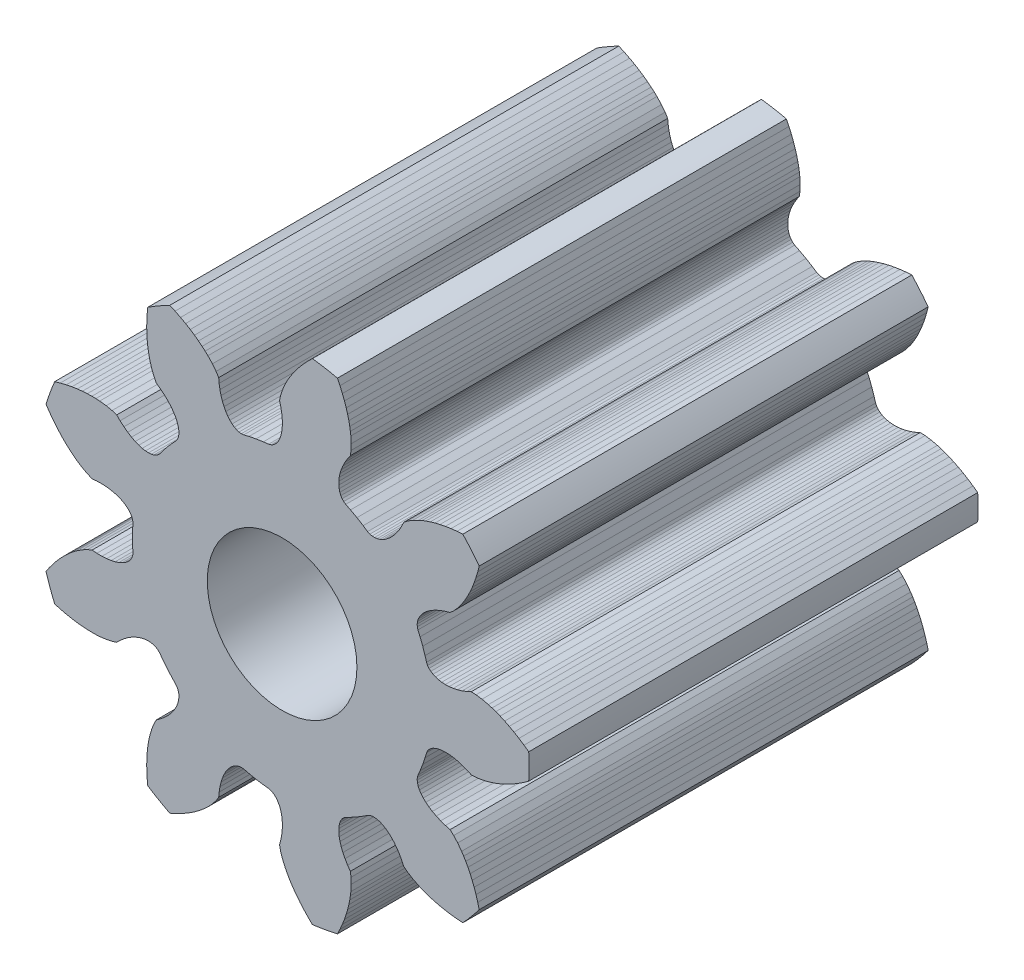
SolidWorks part; units mm, degrees
ref_plane "Plano frontal" through (0, 0, 0) normal (0, 0, 1) x (1, 0, 0)
ref_plane "Plano superior" through (0, 0, 0) normal (0, 1, 0) x (1, 0, 0)
ref_plane "Plano direito" through (0, 0, 0) normal (1, 0, 0) x (0, 0, -1)
sketch "Model" plane through (0, 0, 0) normal (0, 0, 1) x (1, 0, 0)
  line L0 (1.3073, 0.9564) -> (1.2957, 0.9175)
  line L1 (1.2957, 0.9175) -> (1.2833, 0.8811)
  line L2 (1.2833, 0.8811) -> (1.2701, 0.8472)
  line L3 (1.2701, 0.8472) -> (1.2565, 0.8161)
  line L4 (1.2565, 0.8161) -> (1.2419, 0.7863)
  line L5 (1.2419, 0.7863) -> (1.2271, 0.7591)
  line L6 (1.2271, 0.7591) -> (1.2133, 0.7361)
  line L7 (1.2133, 0.7361) -> (1.1993, 0.7148)
  line L8 (1.1993, 0.7148) -> (1.173, 0.6797)
  line L9 (1.173, 0.6797) -> (1.1464, 0.65)
  line L10 (1.1464, 0.65) -> (1.1223, 0.6281)
  line L11 (1.1223, 0.6281) -> (1.0915, 0.6196)
  line L12 (1.0915, 0.6196) -> (1.0595, 0.6085)
  line L13 (1.0595, 0.6085) -> (1.0303, 0.5958)
  line L14 (1.0303, 0.5958) -> (1.0041, 0.5819)
  line L15 (1.0041, 0.5819) -> (0.9808, 0.5669)
  line L16 (0.9808, 0.5669) -> (0.9605, 0.5511)
  line L17 (0.9605, 0.5511) -> (0.9433, 0.5347)
  line L18 (0.9433, 0.5347) -> (0.9291, 0.5179)
  line L19 (0.9291, 0.5179) -> (0.918, 0.501)
  line L20 (0.918, 0.501) -> (0.9099, 0.4841)
  line L21 (0.9099, 0.4841) -> (0.9048, 0.4675)
  line L22 (0.9048, 0.4675) -> (0.9027, 0.4515)
  line L23 (0.9027, 0.4515) -> (0.9034, 0.4362)
  line L24 (0.9034, 0.4362) -> (0.9076, 0.4201)
  line L25 (0.9076, 0.4201) -> (0.9219, 0.3875)
  line L26 (0.9219, 0.3875) -> (0.9397, 0.342)
  line L27 (0.9397, 0.342) -> (0.9553, 0.2957)
  line L28 (0.9553, 0.2957) -> (0.9653, 0.2616)
  line L29 (0.9653, 0.2616) -> (0.9724, 0.2466)
  line L30 (0.9724, 0.2466) -> (0.9817, 0.2344)
  line L31 (0.9817, 0.2344) -> (0.9937, 0.2234)
  line L32 (0.9937, 0.2234) -> (1.0082, 0.214)
  line L33 (1.0082, 0.214) -> (1.0253, 0.2063)
  line L34 (1.0253, 0.2063) -> (1.0447, 0.2005)
  line L35 (1.0447, 0.2005) -> (1.0663, 0.1968)
  line L36 (1.0663, 0.1968) -> (1.0901, 0.1953)
  line L37 (1.0901, 0.1953) -> (1.1158, 0.1962)
  line L38 (1.1158, 0.1962) -> (1.1432, 0.1997)
  line L39 (1.1432, 0.1997) -> (1.1723, 0.2059)
  line L40 (1.1723, 0.2059) -> (1.2027, 0.2149)
  line L41 (1.2027, 0.2149) -> (1.2344, 0.227)
  line L42 (1.2344, 0.227) -> (1.2635, 0.2403)
  line L43 (1.2635, 0.2403) -> (1.296, 0.239)
  line L44 (1.296, 0.239) -> (1.3355, 0.2333)
  line L45 (1.3355, 0.2333) -> (1.3782, 0.2233)
  line L46 (1.3782, 0.2233) -> (1.4026, 0.216)
  line L47 (1.4026, 0.216) -> (1.4279, 0.2073)
  line L48 (1.4279, 0.2073) -> (1.4567, 0.1959)
  line L49 (1.4567, 0.1959) -> (1.4871, 0.1825)
  line L50 (1.4871, 0.1825) -> (1.5175, 0.1674)
  line L51 (1.5175, 0.1674) -> (1.5494, 0.1499)
  line L52 (1.5494, 0.1499) -> (1.5823, 0.1301)
  line L53 (1.5823, 0.1301) -> (1.6162, 0.1077)
  line L54 (1.6162, 0.1077) -> (1.6478, 0.0849)
  line L55 (1.6478, -0.0849) -> (1.6162, -0.1077)
  line L56 (1.6162, -0.1077) -> (1.5823, -0.1301)
  line L57 (1.5823, -0.1301) -> (1.5494, -0.1499)
  line L58 (1.5494, -0.1499) -> (1.5175, -0.1674)
  line L59 (1.5175, -0.1674) -> (1.4871, -0.1825)
  line L60 (1.4871, -0.1825) -> (1.4567, -0.1959)
  line L61 (1.4567, -0.1959) -> (1.4279, -0.2073)
  line L62 (1.4279, -0.2073) -> (1.4026, -0.216)
  line L63 (1.4026, -0.216) -> (1.3782, -0.2233)
  line L64 (1.3782, -0.2233) -> (1.3355, -0.2333)
  line L65 (1.3355, -0.2333) -> (1.296, -0.239)
  line L66 (1.296, -0.239) -> (1.2635, -0.2403)
  line L67 (1.2635, -0.2403) -> (1.2344, -0.227)
  line L68 (1.2344, -0.227) -> (1.2027, -0.2149)
  line L69 (1.2027, -0.2149) -> (1.1723, -0.2059)
  line L70 (1.1723, -0.2059) -> (1.1432, -0.1997)
  line L71 (1.1432, -0.1997) -> (1.1158, -0.1962)
  line L72 (1.1158, -0.1962) -> (1.0901, -0.1953)
  line L73 (1.0901, -0.1953) -> (1.0663, -0.1968)
  line L74 (1.0663, -0.1968) -> (1.0447, -0.2005)
  line L75 (1.0447, -0.2005) -> (1.0253, -0.2063)
  line L76 (1.0253, -0.2063) -> (1.0082, -0.214)
  line L77 (1.0082, -0.214) -> (0.9937, -0.2234)
  line L78 (0.9937, -0.2234) -> (0.9817, -0.2344)
  line L79 (0.9817, -0.2344) -> (0.9724, -0.2466)
  line L80 (0.9724, -0.2466) -> (0.9653, -0.2616)
  line L81 (0.9653, -0.2616) -> (0.9553, -0.2957)
  line L82 (0.9553, -0.2957) -> (0.9397, -0.342)
  line L83 (0.9397, -0.342) -> (0.9219, -0.3875)
  line L84 (0.9219, -0.3875) -> (0.9076, -0.4201)
  line L85 (0.9076, -0.4201) -> (0.9034, -0.4362)
  line L86 (0.9034, -0.4362) -> (0.9027, -0.4515)
  line L87 (0.9027, -0.4515) -> (0.9048, -0.4675)
  line L88 (0.9048, -0.4675) -> (0.9099, -0.4841)
  line L89 (0.9099, -0.4841) -> (0.918, -0.501)
  line L90 (0.918, -0.501) -> (0.9291, -0.5179)
  line L91 (0.9291, -0.5179) -> (0.9433, -0.5347)
  line L92 (0.9433, -0.5347) -> (0.9605, -0.5511)
  line L93 (0.9605, -0.5511) -> (0.9808, -0.5669)
  line L94 (0.9808, -0.5669) -> (1.0041, -0.5819)
  line L95 (1.0041, -0.5819) -> (1.0303, -0.5958)
  line L96 (1.0303, -0.5958) -> (1.0595, -0.6085)
  line L97 (1.0595, -0.6085) -> (1.0915, -0.6196)
  line L98 (1.0915, -0.6196) -> (1.1223, -0.6281)
  line L99 (1.1223, -0.6281) -> (1.1464, -0.65)
  line L100 (1.1464, -0.65) -> (1.173, -0.6797)
  line L101 (1.173, -0.6797) -> (1.1993, -0.7148)
  line L102 (1.1993, -0.7148) -> (1.2133, -0.7361)
  line L103 (1.2133, -0.7361) -> (1.2271, -0.7591)
  line L104 (1.2271, -0.7591) -> (1.2419, -0.7863)
  line L105 (1.2419, -0.7863) -> (1.2565, -0.8161)
  line L106 (1.2565, -0.8161) -> (1.2701, -0.8472)
  line L107 (1.2701, -0.8472) -> (1.2833, -0.8811)
  line L108 (1.2833, -0.8811) -> (1.2957, -0.9175)
  line L109 (1.2957, -0.9175) -> (1.3073, -0.9564)
  line L110 (1.3073, -0.9564) -> (1.3169, -0.9941)
  line L111 (1.2077, -1.1242) -> (1.1689, -1.1214)
  line L112 (1.1689, -1.1214) -> (1.1285, -1.1167)
  line L113 (1.1285, -1.1167) -> (1.0905, -1.1108)
  line L114 (1.0905, -1.1108) -> (1.0549, -1.1037)
  line L115 (1.0549, -1.1037) -> (1.0218, -1.0957)
  line L116 (1.0218, -1.0957) -> (0.99, -1.0865)
  line L117 (0.99, -1.0865) -> (0.9606, -1.0766)
  line L118 (0.9606, -1.0766) -> (0.9356, -1.067)
  line L119 (0.9356, -1.067) -> (0.9122, -1.057)
  line L120 (0.9122, -1.057) -> (0.8731, -1.0372)
  line L121 (0.8731, -1.0372) -> (0.8392, -1.0161)
  line L122 (0.8392, -1.0161) -> (0.8134, -0.9962)
  line L123 (0.8134, -0.9962) -> (0.7997, -0.9674)
  line L124 (0.7997, -0.9674) -> (0.7832, -0.9378)
  line L125 (0.7832, -0.9378) -> (0.7657, -0.9112)
  line L126 (0.7657, -0.9112) -> (0.7474, -0.8878)
  line L127 (0.7474, -0.8878) -> (0.7286, -0.8675)
  line L128 (0.7286, -0.8675) -> (0.7095, -0.8503)
  line L129 (0.7095, -0.8503) -> (0.6904, -0.8361)
  line L130 (0.6904, -0.8361) -> (0.6714, -0.8251)
  line L131 (0.6714, -0.8251) -> (0.6528, -0.8171)
  line L132 (0.6528, -0.8171) -> (0.6348, -0.812)
  line L133 (0.6348, -0.812) -> (0.6176, -0.8099)
  line L134 (0.6176, -0.8099) -> (0.6014, -0.8105)
  line L135 (0.6014, -0.8105) -> (0.5864, -0.8139)
  line L136 (0.5864, -0.8139) -> (0.5713, -0.8209)
  line L137 (0.5713, -0.8209) -> (0.5417, -0.8406)
  line L138 (0.5417, -0.8406) -> (0.5, -0.866)
  line L139 (0.5, -0.866) -> (0.4571, -0.8894)
  line L140 (0.4571, -0.8894) -> (0.4253, -0.9052)
  line L141 (0.4253, -0.9052) -> (0.4117, -0.9148)
  line L142 (0.4117, -0.9148) -> (0.4013, -0.9261)
  line L143 (0.4013, -0.9261) -> (0.3926, -0.9398)
  line L144 (0.3926, -0.9398) -> (0.3858, -0.9557)
  line L145 (0.3858, -0.9557) -> (0.3812, -0.9739)
  line L146 (0.3812, -0.9739) -> (0.3789, -0.994)
  line L147 (0.3789, -0.994) -> (0.3789, -1.016)
  line L148 (0.3789, -1.016) -> (0.3816, -1.0396)
  line L149 (0.3816, -1.0396) -> (0.3869, -1.0647)
  line L150 (0.3869, -1.0647) -> (0.3951, -1.0912)
  line L151 (0.3951, -1.0912) -> (0.4063, -1.1187)
  line L152 (0.4063, -1.1187) -> (0.4205, -1.1472)
  line L153 (0.4205, -1.1472) -> (0.4379, -1.1763)
  line L154 (0.4379, -1.1763) -> (0.456, -1.2025)
  line L155 (0.456, -1.2025) -> (0.4604, -1.2348)
  line L156 (0.4604, -1.2348) -> (0.4617, -1.2747)
  line L157 (0.4617, -1.2747) -> (0.4592, -1.3185)
  line L158 (0.4592, -1.3185) -> (0.4563, -1.3438)
  line L159 (0.4563, -1.3438) -> (0.4521, -1.3702)
  line L160 (0.4521, -1.3702) -> (0.4459, -1.4006)
  line L161 (0.4459, -1.4006) -> (0.4379, -1.4328)
  line L162 (0.4379, -1.4328) -> (0.4284, -1.4654)
  line L163 (0.4284, -1.4654) -> (0.4167, -1.4998)
  line L164 (0.4167, -1.4998) -> (0.4029, -1.5357)
  line L165 (0.4029, -1.5357) -> (0.3867, -1.573)
  line L166 (0.3867, -1.573) -> (0.3698, -1.608)
  line L167 (0.2025, -1.6375) -> (0.1746, -1.6104)
  line L168 (0.1746, -1.6104) -> (0.1467, -1.5809)
  line L169 (0.1467, -1.5809) -> (0.1214, -1.5519)
  line L170 (0.1214, -1.5519) -> (0.0986, -1.5235)
  line L171 (0.0986, -1.5235) -> (0.0785, -1.4962)
  line L172 (0.0785, -1.4962) -> (0.06, -1.4686)
  line L173 (0.06, -1.4686) -> (0.0438, -1.4422)
  line L174 (0.0438, -1.4422) -> (0.0308, -1.4188)
  line L175 (0.0308, -1.4188) -> (0.0194, -1.3961)
  line L176 (0.0194, -1.3961) -> (0.0021, -1.3557)
  line L177 (0.0021, -1.3557) -> (-0.0103, -1.3178)
  line L178 (-0.0103, -1.3178) -> (-0.0172, -1.286)
  line L179 (-0.0172, -1.286) -> (-0.0092, -1.2551)
  line L180 (-0.0092, -1.2551) -> (-0.0028, -1.2218)
  line L181 (-0.0028, -1.2218) -> (0.0008, -1.1902)
  line L182 (0.0008, -1.1902) -> (0.0019, -1.1605)
  line L183 (0.0019, -1.1605) -> (0.0006, -1.1329)
  line L184 (0.0006, -1.1329) -> (-0.003, -1.1074)
  line L185 (-0.003, -1.1074) -> (-0.0086, -1.0843)
  line L186 (-0.0086, -1.0843) -> (-0.016, -1.0636)
  line L187 (-0.016, -1.0636) -> (-0.0252, -1.0455)
  line L188 (-0.0252, -1.0455) -> (-0.0357, -1.0301)
  line L189 (-0.0357, -1.0301) -> (-0.0475, -1.0174)
  line L190 (-0.0475, -1.0174) -> (-0.0603, -1.0075)
  line L191 (-0.0603, -1.0075) -> (-0.074, -1.0005)
  line L192 (-0.074, -1.0005) -> (-0.09, -0.9961)
  line L193 (-0.09, -0.9961) -> (-0.1253, -0.9921)
  line L194 (-0.1253, -0.9921) -> (-0.1736, -0.9848)
  line L195 (-0.1736, -0.9848) -> (-0.2215, -0.9752)
  line L196 (-0.2215, -0.9752) -> (-0.2561, -0.9668)
  line L197 (-0.2561, -0.9668) -> (-0.2727, -0.9654)
  line L198 (-0.2727, -0.9654) -> (-0.2879, -0.9673)
  line L199 (-0.2879, -0.9673) -> (-0.3033, -0.9723)
  line L200 (-0.3033, -0.9723) -> (-0.3188, -0.9801)
  line L201 (-0.3188, -0.9801) -> (-0.334, -0.9911)
  line L202 (-0.334, -0.9911) -> (-0.3487, -1.005)
  line L203 (-0.3487, -1.005) -> (-0.3628, -1.0218)
  line L204 (-0.3628, -1.0218) -> (-0.3759, -1.0417)
  line L205 (-0.3759, -1.0417) -> (-0.388, -1.0644)
  line L206 (-0.388, -1.0644) -> (-0.3987, -1.0899)
  line L207 (-0.3987, -1.0899) -> (-0.4079, -1.1181)
  line L208 (-0.4079, -1.1181) -> (-0.4152, -1.1491)
  line L209 (-0.4152, -1.1491) -> (-0.4207, -1.1825)
  line L210 (-0.4207, -1.1825) -> (-0.4237, -1.2143)
  line L211 (-0.4237, -1.2143) -> (-0.4411, -1.2419)
  line L212 (-0.4411, -1.2419) -> (-0.4657, -1.2732)
  line L213 (-0.4657, -1.2732) -> (-0.4957, -1.3052)
  line L214 (-0.4957, -1.3052) -> (-0.5142, -1.3227)
  line L215 (-0.5142, -1.3227) -> (-0.5345, -1.3402)
  line L216 (-0.5345, -1.3402) -> (-0.5587, -1.3595)
  line L217 (-0.5587, -1.3595) -> (-0.5855, -1.3791)
  line L218 (-0.5855, -1.3791) -> (-0.6138, -1.3979)
  line L219 (-0.6138, -1.3979) -> (-0.6449, -1.4168)
  line L220 (-0.6449, -1.4168) -> (-0.6785, -1.4354)
  line L221 (-0.6785, -1.4354) -> (-0.7149, -1.4535)
  line L222 (-0.7149, -1.4535) -> (-0.7504, -1.4695)
  line L223 (-0.8974, -1.3846) -> (-0.9014, -1.3458)
  line L224 (-0.9014, -1.3458) -> (-0.9038, -1.3053)
  line L225 (-0.9038, -1.3053) -> (-0.9046, -1.2669)
  line L226 (-0.9046, -1.2669) -> (-0.9037, -1.2305)
  line L227 (-0.9037, -1.2305) -> (-0.9016, -1.1966)
  line L228 (-0.9016, -1.1966) -> (-0.898, -1.1636)
  line L229 (-0.898, -1.1636) -> (-0.8934, -1.133)
  line L230 (-0.8934, -1.133) -> (-0.8884, -1.1067)
  line L231 (-0.8884, -1.1067) -> (-0.8825, -1.0819)
  line L232 (-0.8825, -1.0819) -> (-0.8698, -1.0399)
  line L233 (-0.8698, -1.0399) -> (-0.855, -1.0029)
  line L234 (-0.855, -1.0029) -> (-0.8398, -0.9741)
  line L235 (-0.8398, -0.9741) -> (-0.8138, -0.9556)
  line L236 (-0.8138, -0.9556) -> (-0.7875, -0.9341)
  line L237 (-0.7875, -0.9341) -> (-0.7644, -0.9123)
  line L238 (-0.7644, -0.9123) -> (-0.7445, -0.8902)
  line L239 (-0.7445, -0.8902) -> (-0.7278, -0.8682)
  line L240 (-0.7278, -0.8682) -> (-0.7141, -0.8464)
  line L241 (-0.7141, -0.8464) -> (-0.7036, -0.8251)
  line L242 (-0.7036, -0.8251) -> (-0.696, -0.8045)
  line L243 (-0.696, -0.8045) -> (-0.6913, -0.7847)
  line L244 (-0.6913, -0.7847) -> (-0.6895, -0.7661)
  line L245 (-0.6895, -0.7661) -> (-0.6903, -0.7488)
  line L246 (-0.6903, -0.7488) -> (-0.6938, -0.733)
  line L247 (-0.6938, -0.733) -> (-0.6998, -0.7189)
  line L248 (-0.6998, -0.7189) -> (-0.7092, -0.7052)
  line L249 (-0.7092, -0.7052) -> (-0.7337, -0.6794)
  line L250 (-0.7337, -0.6794) -> (-0.766, -0.6428)
  line L251 (-0.766, -0.6428) -> (-0.7965, -0.6046)
  line L252 (-0.7965, -0.6046) -> (-0.8176, -0.576)
  line L253 (-0.8176, -0.576) -> (-0.8294, -0.5643)
  line L254 (-0.8294, -0.5643) -> (-0.8423, -0.556)
  line L255 (-0.8423, -0.556) -> (-0.8573, -0.5498)
  line L256 (-0.8573, -0.5498) -> (-0.8742, -0.5459)
  line L257 (-0.8742, -0.5459) -> (-0.8929, -0.5445)
  line L258 (-0.8929, -0.5445) -> (-0.9131, -0.5457)
  line L259 (-0.9131, -0.5457) -> (-0.9347, -0.5496)
  line L260 (-0.9347, -0.5496) -> (-0.9576, -0.5563)
  line L261 (-0.9576, -0.5563) -> (-0.9814, -0.566)
  line L262 (-0.9814, -0.566) -> (-1.006, -0.5786)
  line L263 (-1.006, -0.5786) -> (-1.0312, -0.5944)
  line L264 (-1.0312, -0.5944) -> (-1.0567, -0.6133)
  line L265 (-1.0567, -0.6133) -> (-1.0824, -0.6355)
  line L266 (-1.0824, -0.6355) -> (-1.1051, -0.6579)
  line L267 (-1.1051, -0.6579) -> (-1.1361, -0.6678)
  line L268 (-1.1361, -0.6678) -> (-1.1752, -0.676)
  line L269 (-1.1752, -0.676) -> (-1.2187, -0.6812)
  line L270 (-1.2187, -0.6812) -> (-1.2441, -0.6827)
  line L271 (-1.2441, -0.6827) -> (-1.2709, -0.6831)
  line L272 (-1.2709, -0.6831) -> (-1.3018, -0.6824)
  line L273 (-1.3018, -0.6824) -> (-1.335, -0.6801)
  line L274 (-1.335, -0.6801) -> (-1.3687, -0.6763)
  line L275 (-1.3687, -0.6763) -> (-1.4047, -0.6708)
  line L276 (-1.4047, -0.6708) -> (-1.4424, -0.6634)
  line L277 (-1.4424, -0.6634) -> (-1.4819, -0.654)
  line L278 (-1.4819, -0.654) -> (-1.5194, -0.6434)
  line L279 (-1.5775, -0.4838) -> (-1.5556, -0.4516)
  line L280 (-1.5556, -0.4516) -> (-1.5314, -0.419)
  line L281 (-1.5314, -0.419) -> (-1.5072, -0.389)
  line L282 (-1.5072, -0.389) -> (-1.4832, -0.3617)
  line L283 (-1.4832, -0.3617) -> (-1.4598, -0.3371)
  line L284 (-1.4598, -0.3371) -> (-1.4359, -0.3141)
  line L285 (-1.4359, -0.3141) -> (-1.4127, -0.2936)
  line L286 (-1.4127, -0.2936) -> (-1.3919, -0.2767)
  line L287 (-1.3919, -0.2767) -> (-1.3715, -0.2615)
  line L288 (-1.3715, -0.2615) -> (-1.3348, -0.2375)
  line L289 (-1.3348, -0.2375) -> (-1.2996, -0.2187)
  line L290 (-1.2996, -0.2187) -> (-1.2694, -0.2064)
  line L291 (-1.2694, -0.2064) -> (-1.2376, -0.2089)
  line L292 (-1.2376, -0.2089) -> (-1.2037, -0.2094)
  line L293 (-1.2037, -0.2094) -> (-1.172, -0.2075)
  line L294 (-1.172, -0.2075) -> (-1.1425, -0.2034)
  line L295 (-1.1425, -0.2034) -> (-1.1156, -0.1973)
  line L296 (-1.1156, -0.1973) -> (-1.0911, -0.1893)
  line L297 (-1.0911, -0.1893) -> (-1.0693, -0.1798)
  line L298 (-1.0693, -0.1798) -> (-1.0502, -0.1689)
  line L299 (-1.0502, -0.1689) -> (-1.034, -0.1568)
  line L300 (-1.034, -0.1568) -> (-1.0206, -0.1437)
  line L301 (-1.0206, -0.1437) -> (-1.0102, -0.1299)
  line L302 (-1.0102, -0.1299) -> (-1.0026, -0.1155)
  line L303 (-1.0026, -0.1155) -> (-0.9981, -0.1009)
  line L304 (-0.9981, -0.1009) -> (-0.9966, -0.0843)
  line L305 (-0.9966, -0.0843) -> (-0.9988, -0.0488)
  line L306 (-0.9988, -0.0488) -> (-1, 0)
  line L307 (-1, 0) -> (-0.9988, 0.0488)
  line L308 (-0.9988, 0.0488) -> (-0.9966, 0.0843)
  line L309 (-0.9966, 0.0843) -> (-0.9981, 0.1009)
  line L310 (-0.9981, 0.1009) -> (-1.0026, 0.1155)
  line L311 (-1.0026, 0.1155) -> (-1.0102, 0.1299)
  line L312 (-1.0102, 0.1299) -> (-1.0206, 0.1437)
  line L313 (-1.0206, 0.1437) -> (-1.034, 0.1568)
  line L314 (-1.034, 0.1568) -> (-1.0502, 0.1689)
  line L315 (-1.0502, 0.1689) -> (-1.0693, 0.1798)
  line L316 (-1.0693, 0.1798) -> (-1.0911, 0.1893)
  line L317 (-1.0911, 0.1893) -> (-1.1156, 0.1973)
  line L318 (-1.1156, 0.1973) -> (-1.1425, 0.2034)
  line L319 (-1.1425, 0.2034) -> (-1.172, 0.2075)
  line L320 (-1.172, 0.2075) -> (-1.2037, 0.2094)
  line L321 (-1.2037, 0.2094) -> (-1.2376, 0.2089)
  line L322 (-1.2376, 0.2089) -> (-1.2694, 0.2064)
  line L323 (-1.2694, 0.2064) -> (-1.2996, 0.2187)
  line L324 (-1.2996, 0.2187) -> (-1.3348, 0.2375)
  line L325 (-1.3348, 0.2375) -> (-1.3715, 0.2615)
  line L326 (-1.3715, 0.2615) -> (-1.3919, 0.2767)
  line L327 (-1.3919, 0.2767) -> (-1.4127, 0.2936)
  line L328 (-1.4127, 0.2936) -> (-1.4359, 0.3141)
  line L329 (-1.4359, 0.3141) -> (-1.4598, 0.3371)
  line L330 (-1.4598, 0.3371) -> (-1.4832, 0.3617)
  line L331 (-1.4832, 0.3617) -> (-1.5072, 0.389)
  line L332 (-1.5072, 0.389) -> (-1.5314, 0.419)
  line L333 (-1.5314, 0.419) -> (-1.5556, 0.4516)
  line L334 (-1.5556, 0.4516) -> (-1.5775, 0.4838)
  line L335 (-1.5194, 0.6434) -> (-1.4819, 0.654)
  line L336 (-1.4819, 0.654) -> (-1.4424, 0.6634)
  line L337 (-1.4424, 0.6634) -> (-1.4047, 0.6708)
  line L338 (-1.4047, 0.6708) -> (-1.3687, 0.6763)
  line L339 (-1.3687, 0.6763) -> (-1.335, 0.6801)
  line L340 (-1.335, 0.6801) -> (-1.3018, 0.6824)
  line L341 (-1.3018, 0.6824) -> (-1.2709, 0.6831)
  line L342 (-1.2709, 0.6831) -> (-1.2441, 0.6827)
  line L343 (-1.2441, 0.6827) -> (-1.2187, 0.6812)
  line L344 (-1.2187, 0.6812) -> (-1.1752, 0.676)
  line L345 (-1.1752, 0.676) -> (-1.1361, 0.6678)
  line L346 (-1.1361, 0.6678) -> (-1.1051, 0.6579)
  line L347 (-1.1051, 0.6579) -> (-1.0824, 0.6355)
  line L348 (-1.0824, 0.6355) -> (-1.0567, 0.6133)
  line L349 (-1.0567, 0.6133) -> (-1.0312, 0.5944)
  line L350 (-1.0312, 0.5944) -> (-1.006, 0.5786)
  line L351 (-1.006, 0.5786) -> (-0.9814, 0.566)
  line L352 (-0.9814, 0.566) -> (-0.9576, 0.5563)
  line L353 (-0.9576, 0.5563) -> (-0.9347, 0.5496)
  line L354 (-0.9347, 0.5496) -> (-0.9131, 0.5457)
  line L355 (-0.9131, 0.5457) -> (-0.8929, 0.5445)
  line L356 (-0.8929, 0.5445) -> (-0.8742, 0.5459)
  line L357 (-0.8742, 0.5459) -> (-0.8573, 0.5498)
  line L358 (-0.8573, 0.5498) -> (-0.8423, 0.556)
  line L359 (-0.8423, 0.556) -> (-0.8294, 0.5643)
  line L360 (-0.8294, 0.5643) -> (-0.8176, 0.576)
  line L361 (-0.8176, 0.576) -> (-0.7965, 0.6046)
  line L362 (-0.7965, 0.6046) -> (-0.766, 0.6428)
  line L363 (-0.766, 0.6428) -> (-0.7337, 0.6794)
  line L364 (-0.7337, 0.6794) -> (-0.7092, 0.7052)
  line L365 (-0.7092, 0.7052) -> (-0.6998, 0.7189)
  line L366 (-0.6998, 0.7189) -> (-0.6938, 0.733)
  line L367 (-0.6938, 0.733) -> (-0.6903, 0.7488)
  line L368 (-0.6903, 0.7488) -> (-0.6895, 0.7661)
  line L369 (-0.6895, 0.7661) -> (-0.6913, 0.7847)
  line L370 (-0.6913, 0.7847) -> (-0.696, 0.8045)
  line L371 (-0.696, 0.8045) -> (-0.7036, 0.8251)
  line L372 (-0.7036, 0.8251) -> (-0.7141, 0.8464)
  line L373 (-0.7141, 0.8464) -> (-0.7278, 0.8682)
  line L374 (-0.7278, 0.8682) -> (-0.7445, 0.8902)
  line L375 (-0.7445, 0.8902) -> (-0.7644, 0.9123)
  line L376 (-0.7644, 0.9123) -> (-0.7875, 0.9341)
  line L377 (-0.7875, 0.9341) -> (-0.8138, 0.9556)
  line L378 (-0.8138, 0.9556) -> (-0.8398, 0.9741)
  line L379 (-0.8398, 0.9741) -> (-0.855, 1.0029)
  line L380 (-0.855, 1.0029) -> (-0.8698, 1.0399)
  line L381 (-0.8698, 1.0399) -> (-0.8825, 1.0819)
  line L382 (-0.8825, 1.0819) -> (-0.8884, 1.1067)
  line L383 (-0.8884, 1.1067) -> (-0.8934, 1.133)
  line L384 (-0.8934, 1.133) -> (-0.898, 1.1636)
  line L385 (-0.898, 1.1636) -> (-0.9016, 1.1966)
  line L386 (-0.9016, 1.1966) -> (-0.9037, 1.2305)
  line L387 (-0.9037, 1.2305) -> (-0.9046, 1.2669)
  line L388 (-0.9046, 1.2669) -> (-0.9038, 1.3053)
  line L389 (-0.9038, 1.3053) -> (-0.9014, 1.3458)
  line L390 (-0.9014, 1.3458) -> (-0.8974, 1.3846)
  line L391 (-0.7504, 1.4695) -> (-0.7149, 1.4535)
  line L392 (-0.7149, 1.4535) -> (-0.6785, 1.4354)
  line L393 (-0.6785, 1.4354) -> (-0.6449, 1.4168)
  line L394 (-0.6449, 1.4168) -> (-0.6138, 1.3979)
  line L395 (-0.6138, 1.3979) -> (-0.5855, 1.3791)
  line L396 (-0.5855, 1.3791) -> (-0.5587, 1.3595)
  line L397 (-0.5587, 1.3595) -> (-0.5345, 1.3402)
  line L398 (-0.5345, 1.3402) -> (-0.5142, 1.3227)
  line L399 (-0.5142, 1.3227) -> (-0.4957, 1.3052)
  line L400 (-0.4957, 1.3052) -> (-0.4657, 1.2732)
  line L401 (-0.4657, 1.2732) -> (-0.4411, 1.2419)
  line L402 (-0.4411, 1.2419) -> (-0.4237, 1.2143)
  line L403 (-0.4237, 1.2143) -> (-0.4207, 1.1825)
  line L404 (-0.4207, 1.1825) -> (-0.4152, 1.1491)
  line L405 (-0.4152, 1.1491) -> (-0.4079, 1.1181)
  line L406 (-0.4079, 1.1181) -> (-0.3987, 1.0899)
  line L407 (-0.3987, 1.0899) -> (-0.388, 1.0644)
  line L408 (-0.388, 1.0644) -> (-0.3759, 1.0417)
  line L409 (-0.3759, 1.0417) -> (-0.3628, 1.0218)
  line L410 (-0.3628, 1.0218) -> (-0.3487, 1.005)
  line L411 (-0.3487, 1.005) -> (-0.334, 0.9911)
  line L412 (-0.334, 0.9911) -> (-0.3188, 0.9801)
  line L413 (-0.3188, 0.9801) -> (-0.3033, 0.9723)
  line L414 (-0.3033, 0.9723) -> (-0.2879, 0.9673)
  line L415 (-0.2879, 0.9673) -> (-0.2727, 0.9654)
  line L416 (-0.2727, 0.9654) -> (-0.2561, 0.9668)
  line L417 (-0.2561, 0.9668) -> (-0.2215, 0.9752)
  line L418 (-0.2215, 0.9752) -> (-0.1736, 0.9848)
  line L419 (-0.1736, 0.9848) -> (-0.1253, 0.9921)
  line L420 (-0.1253, 0.9921) -> (-0.09, 0.9961)
  line L421 (-0.09, 0.9961) -> (-0.074, 1.0005)
  line L422 (-0.074, 1.0005) -> (-0.0603, 1.0075)
  line L423 (-0.0603, 1.0075) -> (-0.0475, 1.0174)
  line L424 (-0.0475, 1.0174) -> (-0.0357, 1.0301)
  line L425 (-0.0357, 1.0301) -> (-0.0252, 1.0455)
  line L426 (-0.0252, 1.0455) -> (-0.016, 1.0636)
  line L427 (-0.016, 1.0636) -> (-0.0086, 1.0843)
  line L428 (-0.0086, 1.0843) -> (-0.003, 1.1074)
  line L429 (-0.003, 1.1074) -> (0.0006, 1.1329)
  line L430 (0.0006, 1.1329) -> (0.0019, 1.1605)
  line L431 (0.0019, 1.1605) -> (0.0008, 1.1902)
  line L432 (0.0008, 1.1902) -> (-0.0028, 1.2218)
  line L433 (-0.0028, 1.2218) -> (-0.0092, 1.2551)
  line L434 (-0.0092, 1.2551) -> (-0.0172, 1.286)
  line L435 (-0.0172, 1.286) -> (-0.0103, 1.3178)
  line L436 (-0.0103, 1.3178) -> (0.0021, 1.3557)
  line L437 (0.0021, 1.3557) -> (0.0194, 1.3961)
  line L438 (0.0194, 1.3961) -> (0.0308, 1.4188)
  line L439 (0.0308, 1.4188) -> (0.0438, 1.4422)
  line L440 (0.0438, 1.4422) -> (0.06, 1.4686)
  line L441 (0.06, 1.4686) -> (0.0785, 1.4962)
  line L442 (0.0785, 1.4962) -> (0.0986, 1.5235)
  line L443 (0.0986, 1.5235) -> (0.1214, 1.5519)
  line L444 (0.1214, 1.5519) -> (0.1467, 1.5809)
  line L445 (0.1467, 1.5809) -> (0.1746, 1.6104)
  line L446 (0.1746, 1.6104) -> (0.2025, 1.6375)
  line L447 (0.3698, 1.608) -> (0.3867, 1.573)
  line L448 (0.3867, 1.573) -> (0.4029, 1.5357)
  line L449 (0.4029, 1.5357) -> (0.4167, 1.4998)
  line L450 (0.4167, 1.4998) -> (0.4284, 1.4654)
  line L451 (0.4284, 1.4654) -> (0.4379, 1.4328)
  line L452 (0.4379, 1.4328) -> (0.4459, 1.4006)
  line L453 (0.4459, 1.4006) -> (0.4521, 1.3702)
  line L454 (0.4521, 1.3702) -> (0.4563, 1.3438)
  line L455 (0.4563, 1.3438) -> (0.4592, 1.3185)
  line L456 (0.4592, 1.3185) -> (0.4617, 1.2747)
  line L457 (0.4617, 1.2747) -> (0.4604, 1.2348)
  line L458 (0.4604, 1.2348) -> (0.456, 1.2025)
  line L459 (0.456, 1.2025) -> (0.4379, 1.1763)
  line L460 (0.4379, 1.1763) -> (0.4205, 1.1472)
  line L461 (0.4205, 1.1472) -> (0.4063, 1.1187)
  line L462 (0.4063, 1.1187) -> (0.3951, 1.0912)
  line L463 (0.3951, 1.0912) -> (0.3869, 1.0647)
  line L464 (0.3869, 1.0647) -> (0.3816, 1.0396)
  line L465 (0.3816, 1.0396) -> (0.3789, 1.016)
  line L466 (0.3789, 1.016) -> (0.3789, 0.994)
  line L467 (0.3789, 0.994) -> (0.3812, 0.9739)
  line L468 (0.3812, 0.9739) -> (0.3858, 0.9557)
  line L469 (0.3858, 0.9557) -> (0.3926, 0.9398)
  line L470 (0.3926, 0.9398) -> (0.4013, 0.9261)
  line L471 (0.4013, 0.9261) -> (0.4117, 0.9148)
  line L472 (0.4117, 0.9148) -> (0.4253, 0.9052)
  line L473 (0.4253, 0.9052) -> (0.4571, 0.8894)
  line L474 (0.4571, 0.8894) -> (0.5, 0.866)
  line L475 (0.5, 0.866) -> (0.5417, 0.8406)
  line L476 (0.5417, 0.8406) -> (0.5713, 0.8209)
  line L477 (0.5713, 0.8209) -> (0.5864, 0.8139)
  line L478 (0.5864, 0.8139) -> (0.6014, 0.8105)
  line L479 (0.6014, 0.8105) -> (0.6176, 0.8099)
  line L480 (0.6176, 0.8099) -> (0.6348, 0.812)
  line L481 (0.6348, 0.812) -> (0.6528, 0.8171)
  line L482 (0.6528, 0.8171) -> (0.6714, 0.8251)
  line L483 (0.6714, 0.8251) -> (0.6904, 0.8361)
  line L484 (0.6904, 0.8361) -> (0.7095, 0.8503)
  line L485 (0.7095, 0.8503) -> (0.7286, 0.8675)
  line L486 (0.7286, 0.8675) -> (0.7474, 0.8878)
  line L487 (0.7474, 0.8878) -> (0.7657, 0.9112)
  line L488 (0.7657, 0.9112) -> (0.7832, 0.9378)
  line L489 (0.7832, 0.9378) -> (0.7997, 0.9674)
  line L490 (0.7997, 0.9674) -> (0.8134, 0.9962)
  line L491 (0.8134, 0.9962) -> (0.8392, 1.0161)
  line L492 (0.8392, 1.0161) -> (0.8731, 1.0372)
  line L493 (0.8731, 1.0372) -> (0.9122, 1.057)
  line L494 (0.9122, 1.057) -> (0.9356, 1.067)
  line L495 (0.9356, 1.067) -> (0.9606, 1.0766)
  line L496 (0.9606, 1.0766) -> (0.99, 1.0865)
  line L497 (0.99, 1.0865) -> (1.0218, 1.0957)
  line L498 (1.0218, 1.0957) -> (1.0549, 1.1037)
  line L499 (1.0549, 1.1037) -> (1.0905, 1.1108)
  line L500 (1.0905, 1.1108) -> (1.1285, 1.1167)
  line L501 (1.1285, 1.1167) -> (1.1689, 1.1214)
  line L502 (1.1689, 1.1214) -> (1.2077, 1.1242)
  line L503 (1.3169, 0.9941) -> (1.3073, 0.9564)
  line L504 (1.3073, 0.9564) -> (1.2957, 0.9175)
  line L505 (1.2957, 0.9175) -> (1.2833, 0.8811)
  line L506 (1.2833, 0.8811) -> (1.2701, 0.8472)
  line L507 (1.2701, 0.8472) -> (1.2565, 0.8161)
  line L508 (1.2565, 0.8161) -> (1.2419, 0.7863)
  line L509 (1.2419, 0.7863) -> (1.2271, 0.7591)
  line L510 (1.2271, 0.7591) -> (1.2133, 0.7361)
  line L511 (1.2133, 0.7361) -> (1.1993, 0.7148)
  line L512 (1.1993, 0.7148) -> (1.173, 0.6797)
  line L513 (1.173, 0.6797) -> (1.1464, 0.65)
  line L514 (1.1464, 0.65) -> (1.1223, 0.6281)
  line L515 (1.1223, 0.6281) -> (1.0915, 0.6196)
  line L516 (1.0915, 0.6196) -> (1.0595, 0.6085)
  line L517 (1.0595, 0.6085) -> (1.0303, 0.5958)
  line L518 (1.0303, 0.5958) -> (1.0041, 0.5819)
  line L519 (1.0041, 0.5819) -> (0.9808, 0.5669)
  line L520 (0.9808, 0.5669) -> (0.9605, 0.5511)
  line L521 (0.9605, 0.5511) -> (0.9433, 0.5347)
  line L522 (0.9433, 0.5347) -> (0.9291, 0.5179)
  line L523 (0.9291, 0.5179) -> (0.918, 0.501)
  line L524 (0.918, 0.501) -> (0.9099, 0.4841)
  line L525 (0.9099, 0.4841) -> (0.9048, 0.4675)
  line L526 (0.9048, 0.4675) -> (0.9027, 0.4515)
  line L527 (0.9027, 0.4515) -> (0.9034, 0.4362)
  line L528 (0.9034, 0.4362) -> (0.9076, 0.4201)
  line L529 (0.9076, 0.4201) -> (0.9219, 0.3875)
  line L530 (0.9219, 0.3875) -> (0.9397, 0.342)
  line L531 (0.9397, 0.342) -> (0.9553, 0.2957)
  line L532 (0.9553, 0.2957) -> (0.9653, 0.2616)
  line L533 (0.9653, 0.2616) -> (0.9724, 0.2466)
  line L534 (0.9724, 0.2466) -> (0.9817, 0.2344)
  line L535 (0.9817, 0.2344) -> (0.9937, 0.2234)
  line L536 (0.9937, 0.2234) -> (1.0082, 0.214)
  line L537 (1.0082, 0.214) -> (1.0253, 0.2063)
  line L538 (1.0253, 0.2063) -> (1.0447, 0.2005)
  line L539 (1.0447, 0.2005) -> (1.0663, 0.1968)
  line L540 (1.0663, 0.1968) -> (1.0901, 0.1953)
  line L541 (1.0901, 0.1953) -> (1.1158, 0.1962)
  line L542 (1.1158, 0.1962) -> (1.1432, 0.1997)
  line L543 (1.1432, 0.1997) -> (1.1723, 0.2059)
  line L544 (1.1723, 0.2059) -> (1.2027, 0.2149)
  line L545 (1.2027, 0.2149) -> (1.2344, 0.227)
  line L546 (1.2344, 0.227) -> (1.2635, 0.2403)
  line L547 (1.2635, 0.2403) -> (1.296, 0.239)
  line L548 (1.296, 0.239) -> (1.3355, 0.2333)
  line L549 (1.3355, 0.2333) -> (1.3782, 0.2233)
  line L550 (1.3782, 0.2233) -> (1.4026, 0.216)
  line L551 (1.4026, 0.216) -> (1.4279, 0.2073)
  line L552 (1.4279, 0.2073) -> (1.4567, 0.1959)
  line L553 (1.4567, 0.1959) -> (1.4871, 0.1825)
  line L554 (1.4871, 0.1825) -> (1.5175, 0.1674)
  line L555 (1.5175, 0.1674) -> (1.5494, 0.1499)
  line L556 (1.5494, 0.1499) -> (1.5823, 0.1301)
  line L557 (1.5823, 0.1301) -> (1.6162, 0.1077)
  line L558 (1.6162, 0.1077) -> (1.6478, 0.0849)
  line L559 (1.6478, -0.0849) -> (1.6162, -0.1077)
  line L560 (1.6162, -0.1077) -> (1.5823, -0.1301)
  line L561 (1.5823, -0.1301) -> (1.5494, -0.1499)
  line L562 (1.5494, -0.1499) -> (1.5175, -0.1674)
  line L563 (1.5175, -0.1674) -> (1.4871, -0.1825)
  line L564 (1.4871, -0.1825) -> (1.4567, -0.1959)
  line L565 (1.4567, -0.1959) -> (1.4279, -0.2073)
  line L566 (1.4279, -0.2073) -> (1.4026, -0.216)
  line L567 (1.4026, -0.216) -> (1.3782, -0.2233)
  line L568 (1.3782, -0.2233) -> (1.3355, -0.2333)
  line L569 (1.3355, -0.2333) -> (1.296, -0.239)
  line L570 (1.296, -0.239) -> (1.2635, -0.2403)
  line L571 (1.2635, -0.2403) -> (1.2344, -0.227)
  line L572 (1.2344, -0.227) -> (1.2027, -0.2149)
  line L573 (1.2027, -0.2149) -> (1.1723, -0.2059)
  line L574 (1.1723, -0.2059) -> (1.1432, -0.1997)
  line L575 (1.1432, -0.1997) -> (1.1158, -0.1962)
  line L576 (1.1158, -0.1962) -> (1.0901, -0.1953)
  line L577 (1.0901, -0.1953) -> (1.0663, -0.1968)
  line L578 (1.0663, -0.1968) -> (1.0447, -0.2005)
  line L579 (1.0447, -0.2005) -> (1.0253, -0.2063)
  line L580 (1.0253, -0.2063) -> (1.0082, -0.214)
  line L581 (1.0082, -0.214) -> (0.9937, -0.2234)
  line L582 (0.9937, -0.2234) -> (0.9817, -0.2344)
  line L583 (0.9817, -0.2344) -> (0.9724, -0.2466)
  line L584 (0.9724, -0.2466) -> (0.9653, -0.2616)
  line L585 (0.9653, -0.2616) -> (0.9553, -0.2957)
  line L586 (0.9553, -0.2957) -> (0.9397, -0.342)
  line L587 (0.9397, -0.342) -> (0.9219, -0.3875)
  line L588 (0.9219, -0.3875) -> (0.9076, -0.4201)
  line L589 (0.9076, -0.4201) -> (0.9034, -0.4362)
  line L590 (0.9034, -0.4362) -> (0.9027, -0.4515)
  line L591 (0.9027, -0.4515) -> (0.9048, -0.4675)
  line L592 (0.9048, -0.4675) -> (0.9099, -0.4841)
  line L593 (0.9099, -0.4841) -> (0.918, -0.501)
  line L594 (0.918, -0.501) -> (0.9291, -0.5179)
  line L595 (0.9291, -0.5179) -> (0.9433, -0.5347)
  line L596 (0.9433, -0.5347) -> (0.9605, -0.5511)
  line L597 (0.9605, -0.5511) -> (0.9808, -0.5669)
  line L598 (0.9808, -0.5669) -> (1.0041, -0.5819)
  line L599 (1.0041, -0.5819) -> (1.0303, -0.5958)
  line L600 (1.0303, -0.5958) -> (1.0595, -0.6085)
  line L601 (1.0595, -0.6085) -> (1.0915, -0.6196)
  line L602 (1.0915, -0.6196) -> (1.1223, -0.6281)
  line L603 (1.1223, -0.6281) -> (1.1464, -0.65)
  line L604 (1.1464, -0.65) -> (1.173, -0.6797)
  line L605 (1.173, -0.6797) -> (1.1993, -0.7148)
  line L606 (1.1993, -0.7148) -> (1.2133, -0.7361)
  line L607 (1.2133, -0.7361) -> (1.2271, -0.7591)
  line L608 (1.2271, -0.7591) -> (1.2419, -0.7863)
  line L609 (1.2419, -0.7863) -> (1.2565, -0.8161)
  line L610 (1.2565, -0.8161) -> (1.2701, -0.8472)
  line L611 (1.2701, -0.8472) -> (1.2833, -0.8811)
  line L612 (1.2833, -0.8811) -> (1.2957, -0.9175)
  line L613 (1.2957, -0.9175) -> (1.3073, -0.9564)
  line L614 (1.3073, -0.9564) -> (1.3169, -0.9941)
  line L615 (1.2077, -1.1242) -> (1.1689, -1.1214)
  line L616 (1.1689, -1.1214) -> (1.1285, -1.1167)
  line L617 (1.1285, -1.1167) -> (1.0905, -1.1108)
  line L618 (1.0905, -1.1108) -> (1.0549, -1.1037)
  line L619 (1.0549, -1.1037) -> (1.0218, -1.0957)
  line L620 (1.0218, -1.0957) -> (0.99, -1.0865)
  line L621 (0.99, -1.0865) -> (0.9606, -1.0766)
  line L622 (0.9606, -1.0766) -> (0.9356, -1.067)
  line L623 (0.9356, -1.067) -> (0.9122, -1.057)
  line L624 (0.9122, -1.057) -> (0.8731, -1.0372)
  line L625 (0.8731, -1.0372) -> (0.8392, -1.0161)
  line L626 (0.8392, -1.0161) -> (0.8134, -0.9962)
  line L627 (0.8134, -0.9962) -> (0.7997, -0.9674)
  line L628 (0.7997, -0.9674) -> (0.7832, -0.9378)
  line L629 (0.7832, -0.9378) -> (0.7657, -0.9112)
  line L630 (0.7657, -0.9112) -> (0.7474, -0.8878)
  line L631 (0.7474, -0.8878) -> (0.7286, -0.8675)
  line L632 (0.7286, -0.8675) -> (0.7095, -0.8503)
  line L633 (0.7095, -0.8503) -> (0.6904, -0.8361)
  line L634 (0.6904, -0.8361) -> (0.6714, -0.8251)
  line L635 (0.6714, -0.8251) -> (0.6528, -0.8171)
  line L636 (0.6528, -0.8171) -> (0.6348, -0.812)
  line L637 (0.6348, -0.812) -> (0.6176, -0.8099)
  line L638 (0.6176, -0.8099) -> (0.6014, -0.8105)
  line L639 (0.6014, -0.8105) -> (0.5864, -0.8139)
  line L640 (0.5864, -0.8139) -> (0.5713, -0.8209)
  line L641 (0.5713, -0.8209) -> (0.5417, -0.8406)
  line L642 (0.5417, -0.8406) -> (0.5, -0.866)
  line L643 (0.5, -0.866) -> (0.4571, -0.8894)
  line L644 (0.4571, -0.8894) -> (0.4253, -0.9052)
  line L645 (0.4253, -0.9052) -> (0.4117, -0.9148)
  line L646 (0.4117, -0.9148) -> (0.4013, -0.9261)
  line L647 (0.4013, -0.9261) -> (0.3926, -0.9398)
  line L648 (0.3926, -0.9398) -> (0.3858, -0.9557)
  line L649 (0.3858, -0.9557) -> (0.3812, -0.9739)
  line L650 (0.3812, -0.9739) -> (0.3789, -0.994)
  line L651 (0.3789, -0.994) -> (0.3789, -1.016)
  line L652 (0.3789, -1.016) -> (0.3816, -1.0396)
  line L653 (0.3816, -1.0396) -> (0.3869, -1.0647)
  line L654 (0.3869, -1.0647) -> (0.3951, -1.0912)
  line L655 (0.3951, -1.0912) -> (0.4063, -1.1187)
  line L656 (0.4063, -1.1187) -> (0.4205, -1.1472)
  line L657 (0.4205, -1.1472) -> (0.4379, -1.1763)
  line L658 (0.4379, -1.1763) -> (0.456, -1.2025)
  line L659 (0.456, -1.2025) -> (0.4604, -1.2348)
  line L660 (0.4604, -1.2348) -> (0.4617, -1.2747)
  line L661 (0.4617, -1.2747) -> (0.4592, -1.3185)
  line L662 (0.4592, -1.3185) -> (0.4563, -1.3438)
  line L663 (0.4563, -1.3438) -> (0.4521, -1.3702)
  line L664 (0.4521, -1.3702) -> (0.4459, -1.4006)
  line L665 (0.4459, -1.4006) -> (0.4379, -1.4328)
  line L666 (0.4379, -1.4328) -> (0.4284, -1.4654)
  line L667 (0.4284, -1.4654) -> (0.4167, -1.4998)
  line L668 (0.4167, -1.4998) -> (0.4029, -1.5357)
  line L669 (0.4029, -1.5357) -> (0.3867, -1.573)
  line L670 (0.3867, -1.573) -> (0.3698, -1.608)
  line L671 (0.2025, -1.6375) -> (0.1746, -1.6104)
  line L672 (0.1746, -1.6104) -> (0.1467, -1.5809)
  line L673 (0.1467, -1.5809) -> (0.1214, -1.5519)
  line L674 (0.1214, -1.5519) -> (0.0986, -1.5235)
  line L675 (0.0986, -1.5235) -> (0.0785, -1.4962)
  line L676 (0.0785, -1.4962) -> (0.06, -1.4686)
  line L677 (0.06, -1.4686) -> (0.0438, -1.4422)
  line L678 (0.0438, -1.4422) -> (0.0308, -1.4188)
  line L679 (0.0308, -1.4188) -> (0.0194, -1.3961)
  line L680 (0.0194, -1.3961) -> (0.0021, -1.3557)
  line L681 (0.0021, -1.3557) -> (-0.0103, -1.3178)
  line L682 (-0.0103, -1.3178) -> (-0.0172, -1.286)
  line L683 (-0.0172, -1.286) -> (-0.0092, -1.2551)
  line L684 (-0.0092, -1.2551) -> (-0.0028, -1.2218)
  line L685 (-0.0028, -1.2218) -> (0.0008, -1.1902)
  line L686 (0.0008, -1.1902) -> (0.0019, -1.1605)
  line L687 (0.0019, -1.1605) -> (0.0006, -1.1329)
  line L688 (0.0006, -1.1329) -> (-0.003, -1.1074)
  line L689 (-0.003, -1.1074) -> (-0.0086, -1.0843)
  line L690 (-0.0086, -1.0843) -> (-0.016, -1.0636)
  line L691 (-0.016, -1.0636) -> (-0.0252, -1.0455)
  line L692 (-0.0252, -1.0455) -> (-0.0357, -1.0301)
  line L693 (-0.0357, -1.0301) -> (-0.0475, -1.0174)
  line L694 (-0.0475, -1.0174) -> (-0.0603, -1.0075)
  line L695 (-0.0603, -1.0075) -> (-0.074, -1.0005)
  line L696 (-0.074, -1.0005) -> (-0.09, -0.9961)
  line L697 (-0.09, -0.9961) -> (-0.1253, -0.9921)
  line L698 (-0.1253, -0.9921) -> (-0.1736, -0.9848)
  line L699 (-0.1736, -0.9848) -> (-0.2215, -0.9752)
  line L700 (-0.2215, -0.9752) -> (-0.2561, -0.9668)
  line L701 (-0.2561, -0.9668) -> (-0.2727, -0.9654)
  line L702 (-0.2727, -0.9654) -> (-0.2879, -0.9673)
  line L703 (-0.2879, -0.9673) -> (-0.3033, -0.9723)
  line L704 (-0.3033, -0.9723) -> (-0.3188, -0.9801)
  line L705 (-0.3188, -0.9801) -> (-0.334, -0.9911)
  line L706 (-0.334, -0.9911) -> (-0.3487, -1.005)
  line L707 (-0.3487, -1.005) -> (-0.3628, -1.0218)
  line L708 (-0.3628, -1.0218) -> (-0.3759, -1.0417)
  line L709 (-0.3759, -1.0417) -> (-0.388, -1.0644)
  line L710 (-0.388, -1.0644) -> (-0.3987, -1.0899)
  line L711 (-0.3987, -1.0899) -> (-0.4079, -1.1181)
  line L712 (-0.4079, -1.1181) -> (-0.4152, -1.1491)
  line L713 (-0.4152, -1.1491) -> (-0.4207, -1.1825)
  line L714 (-0.4207, -1.1825) -> (-0.4237, -1.2143)
  line L715 (-0.4237, -1.2143) -> (-0.4411, -1.2419)
  line L716 (-0.4411, -1.2419) -> (-0.4657, -1.2732)
  line L717 (-0.4657, -1.2732) -> (-0.4957, -1.3052)
  line L718 (-0.4957, -1.3052) -> (-0.5142, -1.3227)
  line L719 (-0.5142, -1.3227) -> (-0.5345, -1.3402)
  line L720 (-0.5345, -1.3402) -> (-0.5587, -1.3595)
  line L721 (-0.5587, -1.3595) -> (-0.5855, -1.3791)
  line L722 (-0.5855, -1.3791) -> (-0.6138, -1.3979)
  line L723 (-0.6138, -1.3979) -> (-0.6449, -1.4168)
  line L724 (-0.6449, -1.4168) -> (-0.6785, -1.4354)
  line L725 (-0.6785, -1.4354) -> (-0.7149, -1.4535)
  line L726 (-0.7149, -1.4535) -> (-0.7504, -1.4695)
  line L727 (-0.8974, -1.3846) -> (-0.9014, -1.3458)
  line L728 (-0.9014, -1.3458) -> (-0.9038, -1.3053)
  line L729 (-0.9038, -1.3053) -> (-0.9046, -1.2669)
  line L730 (-0.9046, -1.2669) -> (-0.9037, -1.2305)
  line L731 (-0.9037, -1.2305) -> (-0.9016, -1.1966)
  line L732 (-0.9016, -1.1966) -> (-0.898, -1.1636)
  line L733 (-0.898, -1.1636) -> (-0.8934, -1.133)
  line L734 (-0.8934, -1.133) -> (-0.8884, -1.1067)
  line L735 (-0.8884, -1.1067) -> (-0.8825, -1.0819)
  line L736 (-0.8825, -1.0819) -> (-0.8698, -1.0399)
  line L737 (-0.8698, -1.0399) -> (-0.855, -1.0029)
  line L738 (-0.855, -1.0029) -> (-0.8398, -0.9741)
  line L739 (-0.8398, -0.9741) -> (-0.8138, -0.9556)
  line L740 (-0.8138, -0.9556) -> (-0.7875, -0.9341)
  line L741 (-0.7875, -0.9341) -> (-0.7644, -0.9123)
  line L742 (-0.7644, -0.9123) -> (-0.7445, -0.8902)
  line L743 (-0.7445, -0.8902) -> (-0.7278, -0.8682)
  line L744 (-0.7278, -0.8682) -> (-0.7141, -0.8464)
  line L745 (-0.7141, -0.8464) -> (-0.7036, -0.8251)
  line L746 (-0.7036, -0.8251) -> (-0.696, -0.8045)
  line L747 (-0.696, -0.8045) -> (-0.6913, -0.7847)
  line L748 (-0.6913, -0.7847) -> (-0.6895, -0.7661)
  line L749 (-0.6895, -0.7661) -> (-0.6903, -0.7488)
  line L750 (-0.6903, -0.7488) -> (-0.6938, -0.733)
  line L751 (-0.6938, -0.733) -> (-0.6998, -0.7189)
  line L752 (-0.6998, -0.7189) -> (-0.7092, -0.7052)
  line L753 (-0.7092, -0.7052) -> (-0.7337, -0.6794)
  line L754 (-0.7337, -0.6794) -> (-0.766, -0.6428)
  line L755 (-0.766, -0.6428) -> (-0.7965, -0.6046)
  line L756 (-0.7965, -0.6046) -> (-0.8176, -0.576)
  line L757 (-0.8176, -0.576) -> (-0.8294, -0.5643)
  line L758 (-0.8294, -0.5643) -> (-0.8423, -0.556)
  line L759 (-0.8423, -0.556) -> (-0.8573, -0.5498)
  line L760 (-0.8573, -0.5498) -> (-0.8742, -0.5459)
  line L761 (-0.8742, -0.5459) -> (-0.8929, -0.5445)
  line L762 (-0.8929, -0.5445) -> (-0.9131, -0.5457)
  line L763 (-0.9131, -0.5457) -> (-0.9347, -0.5496)
  line L764 (-0.9347, -0.5496) -> (-0.9576, -0.5563)
  line L765 (-0.9576, -0.5563) -> (-0.9814, -0.566)
  line L766 (-0.9814, -0.566) -> (-1.006, -0.5786)
  line L767 (-1.006, -0.5786) -> (-1.0312, -0.5944)
  line L768 (-1.0312, -0.5944) -> (-1.0567, -0.6133)
  line L769 (-1.0567, -0.6133) -> (-1.0824, -0.6355)
  line L770 (-1.0824, -0.6355) -> (-1.1051, -0.6579)
  line L771 (-1.1051, -0.6579) -> (-1.1361, -0.6678)
  line L772 (-1.1361, -0.6678) -> (-1.1752, -0.676)
  line L773 (-1.1752, -0.676) -> (-1.2187, -0.6812)
  line L774 (-1.2187, -0.6812) -> (-1.2441, -0.6827)
  line L775 (-1.2441, -0.6827) -> (-1.2709, -0.6831)
  line L776 (-1.2709, -0.6831) -> (-1.3018, -0.6824)
  line L777 (-1.3018, -0.6824) -> (-1.335, -0.6801)
  line L778 (-1.335, -0.6801) -> (-1.3687, -0.6763)
  line L779 (-1.3687, -0.6763) -> (-1.4047, -0.6708)
  line L780 (-1.4047, -0.6708) -> (-1.4424, -0.6634)
  line L781 (-1.4424, -0.6634) -> (-1.4819, -0.654)
  line L782 (-1.4819, -0.654) -> (-1.5194, -0.6434)
  line L783 (-1.5775, -0.4838) -> (-1.5556, -0.4516)
  line L784 (-1.5556, -0.4516) -> (-1.5314, -0.419)
  line L785 (-1.5314, -0.419) -> (-1.5072, -0.389)
  line L786 (-1.5072, -0.389) -> (-1.4832, -0.3617)
  line L787 (-1.4832, -0.3617) -> (-1.4598, -0.3371)
  line L788 (-1.4598, -0.3371) -> (-1.4359, -0.3141)
  line L789 (-1.4359, -0.3141) -> (-1.4127, -0.2936)
  line L790 (-1.4127, -0.2936) -> (-1.3919, -0.2767)
  line L791 (-1.3919, -0.2767) -> (-1.3715, -0.2615)
  line L792 (-1.3715, -0.2615) -> (-1.3348, -0.2375)
  line L793 (-1.3348, -0.2375) -> (-1.2996, -0.2187)
  line L794 (-1.2996, -0.2187) -> (-1.2694, -0.2064)
  line L795 (-1.2694, -0.2064) -> (-1.2376, -0.2089)
  line L796 (-1.2376, -0.2089) -> (-1.2037, -0.2094)
  line L797 (-1.2037, -0.2094) -> (-1.172, -0.2075)
  line L798 (-1.172, -0.2075) -> (-1.1425, -0.2034)
  line L799 (-1.1425, -0.2034) -> (-1.1156, -0.1973)
  line L800 (-1.1156, -0.1973) -> (-1.0911, -0.1893)
  line L801 (-1.0911, -0.1893) -> (-1.0693, -0.1798)
  line L802 (-1.0693, -0.1798) -> (-1.0502, -0.1689)
  line L803 (-1.0502, -0.1689) -> (-1.034, -0.1568)
  line L804 (-1.034, -0.1568) -> (-1.0206, -0.1437)
  line L805 (-1.0206, -0.1437) -> (-1.0102, -0.1299)
  line L806 (-1.0102, -0.1299) -> (-1.0026, -0.1155)
  line L807 (-1.0026, -0.1155) -> (-0.9981, -0.1009)
  line L808 (-0.9981, -0.1009) -> (-0.9966, -0.0843)
  line L809 (-0.9966, -0.0843) -> (-0.9988, -0.0488)
  line L810 (-0.9988, -0.0488) -> (-1, 0)
  line L811 (-1, 0) -> (-0.9988, 0.0488)
  line L812 (-0.9988, 0.0488) -> (-0.9966, 0.0843)
  line L813 (-0.9966, 0.0843) -> (-0.9981, 0.1009)
  line L814 (-0.9981, 0.1009) -> (-1.0026, 0.1155)
  line L815 (-1.0026, 0.1155) -> (-1.0102, 0.1299)
  line L816 (-1.0102, 0.1299) -> (-1.0206, 0.1437)
  line L817 (-1.0206, 0.1437) -> (-1.034, 0.1568)
  line L818 (-1.034, 0.1568) -> (-1.0502, 0.1689)
  line L819 (-1.0502, 0.1689) -> (-1.0693, 0.1798)
  line L820 (-1.0693, 0.1798) -> (-1.0911, 0.1893)
  line L821 (-1.0911, 0.1893) -> (-1.1156, 0.1973)
  line L822 (-1.1156, 0.1973) -> (-1.1425, 0.2034)
  line L823 (-1.1425, 0.2034) -> (-1.172, 0.2075)
  line L824 (-1.172, 0.2075) -> (-1.2037, 0.2094)
  line L825 (-1.2037, 0.2094) -> (-1.2376, 0.2089)
  line L826 (-1.2376, 0.2089) -> (-1.2694, 0.2064)
  line L827 (-1.2694, 0.2064) -> (-1.2996, 0.2187)
  line L828 (-1.2996, 0.2187) -> (-1.3348, 0.2375)
  line L829 (-1.3348, 0.2375) -> (-1.3715, 0.2615)
  line L830 (-1.3715, 0.2615) -> (-1.3919, 0.2767)
  line L831 (-1.3919, 0.2767) -> (-1.4127, 0.2936)
  line L832 (-1.4127, 0.2936) -> (-1.4359, 0.3141)
  line L833 (-1.4359, 0.3141) -> (-1.4598, 0.3371)
  line L834 (-1.4598, 0.3371) -> (-1.4832, 0.3617)
  line L835 (-1.4832, 0.3617) -> (-1.5072, 0.389)
  line L836 (-1.5072, 0.389) -> (-1.5314, 0.419)
  line L837 (-1.5314, 0.419) -> (-1.5556, 0.4516)
  line L838 (-1.5556, 0.4516) -> (-1.5775, 0.4838)
  line L839 (-1.5194, 0.6434) -> (-1.4819, 0.654)
  line L840 (-1.4819, 0.654) -> (-1.4424, 0.6634)
  line L841 (-1.4424, 0.6634) -> (-1.4047, 0.6708)
  line L842 (-1.4047, 0.6708) -> (-1.3687, 0.6763)
  line L843 (-1.3687, 0.6763) -> (-1.335, 0.6801)
  line L844 (-1.335, 0.6801) -> (-1.3018, 0.6824)
  line L845 (-1.3018, 0.6824) -> (-1.2709, 0.6831)
  line L846 (-1.2709, 0.6831) -> (-1.2441, 0.6827)
  line L847 (-1.2441, 0.6827) -> (-1.2187, 0.6812)
  line L848 (-1.2187, 0.6812) -> (-1.1752, 0.676)
  line L849 (-1.1752, 0.676) -> (-1.1361, 0.6678)
  line L850 (-1.1361, 0.6678) -> (-1.1051, 0.6579)
  line L851 (-1.1051, 0.6579) -> (-1.0824, 0.6355)
  line L852 (-1.0824, 0.6355) -> (-1.0567, 0.6133)
  line L853 (-1.0567, 0.6133) -> (-1.0312, 0.5944)
  line L854 (-1.0312, 0.5944) -> (-1.006, 0.5786)
  line L855 (-1.006, 0.5786) -> (-0.9814, 0.566)
  line L856 (-0.9814, 0.566) -> (-0.9576, 0.5563)
  line L857 (-0.9576, 0.5563) -> (-0.9347, 0.5496)
  line L858 (-0.9347, 0.5496) -> (-0.9131, 0.5457)
  line L859 (-0.9131, 0.5457) -> (-0.8929, 0.5445)
  line L860 (-0.8929, 0.5445) -> (-0.8742, 0.5459)
  line L861 (-0.8742, 0.5459) -> (-0.8573, 0.5498)
  line L862 (-0.8573, 0.5498) -> (-0.8423, 0.556)
  line L863 (-0.8423, 0.556) -> (-0.8294, 0.5643)
  line L864 (-0.8294, 0.5643) -> (-0.8176, 0.576)
  line L865 (-0.8176, 0.576) -> (-0.7965, 0.6046)
  line L866 (-0.7965, 0.6046) -> (-0.766, 0.6428)
  line L867 (-0.766, 0.6428) -> (-0.7337, 0.6794)
  line L868 (-0.7337, 0.6794) -> (-0.7092, 0.7052)
  line L869 (-0.7092, 0.7052) -> (-0.6998, 0.7189)
  line L870 (-0.6998, 0.7189) -> (-0.6938, 0.733)
  line L871 (-0.6938, 0.733) -> (-0.6903, 0.7488)
  line L872 (-0.6903, 0.7488) -> (-0.6895, 0.7661)
  line L873 (-0.6895, 0.7661) -> (-0.6913, 0.7847)
  line L874 (-0.6913, 0.7847) -> (-0.696, 0.8045)
  line L875 (-0.696, 0.8045) -> (-0.7036, 0.8251)
  line L876 (-0.7036, 0.8251) -> (-0.7141, 0.8464)
  line L877 (-0.7141, 0.8464) -> (-0.7278, 0.8682)
  line L878 (-0.7278, 0.8682) -> (-0.7445, 0.8902)
  line L879 (-0.7445, 0.8902) -> (-0.7644, 0.9123)
  line L880 (-0.7644, 0.9123) -> (-0.7875, 0.9341)
  line L881 (-0.7875, 0.9341) -> (-0.8138, 0.9556)
  line L882 (-0.8138, 0.9556) -> (-0.8398, 0.9741)
  line L883 (-0.8398, 0.9741) -> (-0.855, 1.0029)
  line L884 (-0.855, 1.0029) -> (-0.8698, 1.0399)
  line L885 (-0.8698, 1.0399) -> (-0.8825, 1.0819)
  line L886 (-0.8825, 1.0819) -> (-0.8884, 1.1067)
  line L887 (-0.8884, 1.1067) -> (-0.8934, 1.133)
  line L888 (-0.8934, 1.133) -> (-0.898, 1.1636)
  line L889 (-0.898, 1.1636) -> (-0.9016, 1.1966)
  line L890 (-0.9016, 1.1966) -> (-0.9037, 1.2305)
  line L891 (-0.9037, 1.2305) -> (-0.9046, 1.2669)
  line L892 (-0.9046, 1.2669) -> (-0.9038, 1.3053)
  line L893 (-0.9038, 1.3053) -> (-0.9014, 1.3458)
  line L894 (-0.9014, 1.3458) -> (-0.8974, 1.3846)
  line L895 (-0.7504, 1.4695) -> (-0.7149, 1.4535)
  line L896 (-0.7149, 1.4535) -> (-0.6785, 1.4354)
  line L897 (-0.6785, 1.4354) -> (-0.6449, 1.4168)
  line L898 (-0.6449, 1.4168) -> (-0.6138, 1.3979)
  line L899 (-0.6138, 1.3979) -> (-0.5855, 1.3791)
  line L900 (-0.5855, 1.3791) -> (-0.5587, 1.3595)
  line L901 (-0.5587, 1.3595) -> (-0.5345, 1.3402)
  line L902 (-0.5345, 1.3402) -> (-0.5142, 1.3227)
  line L903 (-0.5142, 1.3227) -> (-0.4957, 1.3052)
  line L904 (-0.4957, 1.3052) -> (-0.4657, 1.2732)
  line L905 (-0.4657, 1.2732) -> (-0.4411, 1.2419)
  line L906 (-0.4411, 1.2419) -> (-0.4237, 1.2143)
  line L907 (-0.4237, 1.2143) -> (-0.4207, 1.1825)
  line L908 (-0.4207, 1.1825) -> (-0.4152, 1.1491)
  line L909 (-0.4152, 1.1491) -> (-0.4079, 1.1181)
  line L910 (-0.4079, 1.1181) -> (-0.3987, 1.0899)
  line L911 (-0.3987, 1.0899) -> (-0.388, 1.0644)
  line L912 (-0.388, 1.0644) -> (-0.3759, 1.0417)
  line L913 (-0.3759, 1.0417) -> (-0.3628, 1.0218)
  line L914 (-0.3628, 1.0218) -> (-0.3487, 1.005)
  line L915 (-0.3487, 1.005) -> (-0.334, 0.9911)
  line L916 (-0.334, 0.9911) -> (-0.3188, 0.9801)
  line L917 (-0.3188, 0.9801) -> (-0.3033, 0.9723)
  line L918 (-0.3033, 0.9723) -> (-0.2879, 0.9673)
  line L919 (-0.2879, 0.9673) -> (-0.2727, 0.9654)
  line L920 (-0.2727, 0.9654) -> (-0.2561, 0.9668)
  line L921 (-0.2561, 0.9668) -> (-0.2215, 0.9752)
  line L922 (-0.2215, 0.9752) -> (-0.1736, 0.9848)
  line L923 (-0.1736, 0.9848) -> (-0.1253, 0.9921)
  line L924 (-0.1253, 0.9921) -> (-0.09, 0.9961)
  line L925 (-0.09, 0.9961) -> (-0.074, 1.0005)
  line L926 (-0.074, 1.0005) -> (-0.0603, 1.0075)
  line L927 (-0.0603, 1.0075) -> (-0.0475, 1.0174)
  line L928 (-0.0475, 1.0174) -> (-0.0357, 1.0301)
  line L929 (-0.0357, 1.0301) -> (-0.0252, 1.0455)
  line L930 (-0.0252, 1.0455) -> (-0.016, 1.0636)
  line L931 (-0.016, 1.0636) -> (-0.0086, 1.0843)
  line L932 (-0.0086, 1.0843) -> (-0.003, 1.1074)
  line L933 (-0.003, 1.1074) -> (0.0006, 1.1329)
  line L934 (0.0006, 1.1329) -> (0.0019, 1.1605)
  line L935 (0.0019, 1.1605) -> (0.0008, 1.1902)
  line L936 (0.0008, 1.1902) -> (-0.0028, 1.2218)
  line L937 (-0.0028, 1.2218) -> (-0.0092, 1.2551)
  line L938 (-0.0092, 1.2551) -> (-0.0172, 1.286)
  line L939 (-0.0172, 1.286) -> (-0.0103, 1.3178)
  line L940 (-0.0103, 1.3178) -> (0.0021, 1.3557)
  line L941 (0.0021, 1.3557) -> (0.0194, 1.3961)
  line L942 (0.0194, 1.3961) -> (0.0308, 1.4188)
  line L943 (0.0308, 1.4188) -> (0.0438, 1.4422)
  line L944 (0.0438, 1.4422) -> (0.06, 1.4686)
  line L945 (0.06, 1.4686) -> (0.0785, 1.4962)
  line L946 (0.0785, 1.4962) -> (0.0986, 1.5235)
  line L947 (0.0986, 1.5235) -> (0.1214, 1.5519)
  line L948 (0.1214, 1.5519) -> (0.1467, 1.5809)
  line L949 (0.1467, 1.5809) -> (0.1746, 1.6104)
  line L950 (0.1746, 1.6104) -> (0.2025, 1.6375)
  line L951 (0.3698, 1.608) -> (0.3867, 1.573)
  line L952 (0.3867, 1.573) -> (0.4029, 1.5357)
  line L953 (0.4029, 1.5357) -> (0.4167, 1.4998)
  line L954 (0.4167, 1.4998) -> (0.4284, 1.4654)
  line L955 (0.4284, 1.4654) -> (0.4379, 1.4328)
  line L956 (0.4379, 1.4328) -> (0.4459, 1.4006)
  line L957 (0.4459, 1.4006) -> (0.4521, 1.3702)
  line L958 (0.4521, 1.3702) -> (0.4563, 1.3438)
  line L959 (0.4563, 1.3438) -> (0.4592, 1.3185)
  line L960 (0.4592, 1.3185) -> (0.4617, 1.2747)
  line L961 (0.4617, 1.2747) -> (0.4604, 1.2348)
  line L962 (0.4604, 1.2348) -> (0.456, 1.2025)
  line L963 (0.456, 1.2025) -> (0.4379, 1.1763)
  line L964 (0.4379, 1.1763) -> (0.4205, 1.1472)
  line L965 (0.4205, 1.1472) -> (0.4063, 1.1187)
  line L966 (0.4063, 1.1187) -> (0.3951, 1.0912)
  line L967 (0.3951, 1.0912) -> (0.3869, 1.0647)
  line L968 (0.3869, 1.0647) -> (0.3816, 1.0396)
  line L969 (0.3816, 1.0396) -> (0.3789, 1.016)
  line L970 (0.3789, 1.016) -> (0.3789, 0.994)
  line L971 (0.3789, 0.994) -> (0.3812, 0.9739)
  line L972 (0.3812, 0.9739) -> (0.3858, 0.9557)
  line L973 (0.3858, 0.9557) -> (0.3926, 0.9398)
  line L974 (0.3926, 0.9398) -> (0.4013, 0.9261)
  line L975 (0.4013, 0.9261) -> (0.4117, 0.9148)
  line L976 (0.4117, 0.9148) -> (0.4253, 0.9052)
  line L977 (0.4253, 0.9052) -> (0.4571, 0.8894)
  line L978 (0.4571, 0.8894) -> (0.5, 0.866)
  line L979 (0.5, 0.866) -> (0.5417, 0.8406)
  line L980 (0.5417, 0.8406) -> (0.5713, 0.8209)
  line L981 (0.5713, 0.8209) -> (0.5864, 0.8139)
  line L982 (0.5864, 0.8139) -> (0.6014, 0.8105)
  line L983 (0.6014, 0.8105) -> (0.6176, 0.8099)
  line L984 (0.6176, 0.8099) -> (0.6348, 0.812)
  line L985 (0.6348, 0.812) -> (0.6528, 0.8171)
  line L986 (0.6528, 0.8171) -> (0.6714, 0.8251)
  line L987 (0.6714, 0.8251) -> (0.6904, 0.8361)
  line L988 (0.6904, 0.8361) -> (0.7095, 0.8503)
  line L989 (0.7095, 0.8503) -> (0.7286, 0.8675)
  line L990 (0.7286, 0.8675) -> (0.7474, 0.8878)
  line L991 (0.7474, 0.8878) -> (0.7657, 0.9112)
  line L992 (0.7657, 0.9112) -> (0.7832, 0.9378)
  line L993 (0.7832, 0.9378) -> (0.7997, 0.9674)
  line L994 (0.7997, 0.9674) -> (0.8134, 0.9962)
  line L995 (0.8134, 0.9962) -> (0.8392, 1.0161)
  line L996 (0.8392, 1.0161) -> (0.8731, 1.0372)
  line L997 (0.8731, 1.0372) -> (0.9122, 1.057)
  line L998 (0.9122, 1.057) -> (0.9356, 1.067)
  line L999 (0.9356, 1.067) -> (0.9606, 1.0766)
  line L1000 (0.9606, 1.0766) -> (0.99, 1.0865)
  line L1001 (0.99, 1.0865) -> (1.0218, 1.0957)
  line L1002 (1.0218, 1.0957) -> (1.0549, 1.1037)
  line L1003 (1.0549, 1.1037) -> (1.0905, 1.1108)
  line L1004 (1.0905, 1.1108) -> (1.1285, 1.1167)
  line L1005 (1.1285, 1.1167) -> (1.1689, 1.1214)
  line L1006 (1.1689, 1.1214) -> (1.2077, 1.1242)
  line L1007 (1.3169, 0.9941) -> (1.3073, 0.9564)
  circle A0 centre (0, 0) radius 0.5
  circle A1 centre (0, 0) radius 0.5
  arc A2 (1.6478, -0.0849) -> (1.6478, 0.0849) centre (0, 0) ccw
  arc A3 (1.2077, -1.1242) -> (1.3169, -0.9941) centre (0, 0) ccw
  arc A4 (0.2025, -1.6375) -> (0.3698, -1.608) centre (0, 0) ccw
  arc A5 (-0.8974, -1.3846) -> (-0.7504, -1.4695) centre (0, 0) ccw
  arc A6 (-1.5775, -0.4838) -> (-1.5194, -0.6434) centre (0, 0) ccw
  arc A7 (-1.5194, 0.6434) -> (-1.5775, 0.4838) centre (0, 0) ccw
  arc A8 (-0.7504, 1.4695) -> (-0.8974, 1.3846) centre (0, 0) ccw
  arc A9 (0.3698, 1.608) -> (0.2025, 1.6375) centre (0, 0) ccw
  arc A10 (1.3169, 0.9941) -> (1.2077, 1.1242) centre (0, 0) ccw
  arc A11 (1.6478, -0.0849) -> (1.6478, 0.0849) centre (0, 0) ccw
  arc A12 (1.2077, -1.1242) -> (1.3169, -0.9941) centre (0, 0) ccw
  arc A13 (0.2025, -1.6375) -> (0.3698, -1.608) centre (0, 0) ccw
  arc A14 (-0.8974, -1.3846) -> (-0.7504, -1.4695) centre (0, 0) ccw
  arc A15 (-1.5775, -0.4838) -> (-1.5194, -0.6434) centre (0, 0) ccw
  arc A16 (-1.5194, 0.6434) -> (-1.5775, 0.4838) centre (0, 0) ccw
  arc A17 (-0.7504, 1.4695) -> (-0.8974, 1.3846) centre (0, 0) ccw
  arc A18 (0.3698, 1.608) -> (0.2025, 1.6375) centre (0, 0) ccw
  arc A19 (1.3169, 0.9941) -> (1.2077, 1.1242) centre (0, 0) ccw
extrude "Ressalto-extrusão1" add sketch "Model" along normal blind 3 contours L503 A10 L502 L501 L500 L499 L498 L497 L496 L495 L494 L493 L492 L491 L490 L489 L488 L487 L486 L485 L484 L483 L482 L481 L480 L479 L478 L477 L476 L475 L474 L473 L472 L471 L470 L469 L468 L467 L466 L465 L464 L463 L462 L461 L460 L459 L458 L457 L456 L455 L454 region at (1.2575, 0.95, 0)
